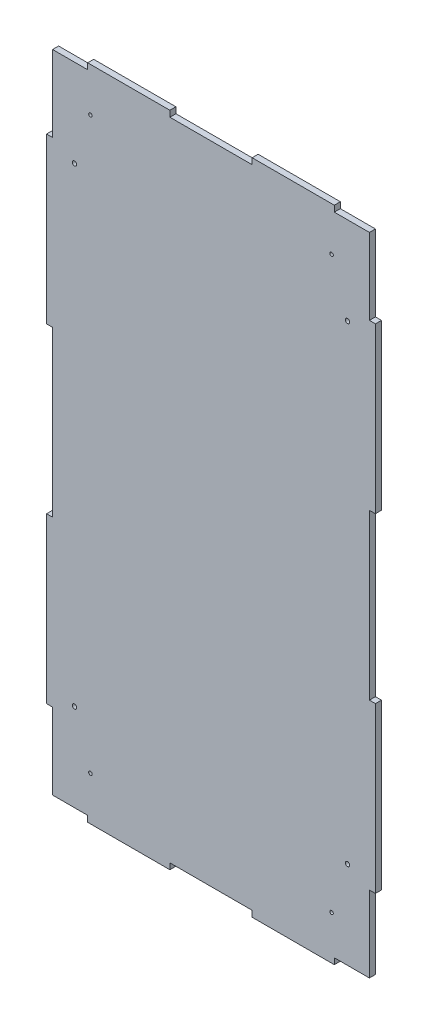
SolidWorks part; units mm, degrees
ref_plane "Front Plane" through (0, 0, 0) normal (0, 0, 1) x (1, 0, 0)
ref_plane "Top Plane" through (0, 0, 0) normal (0, 1, 0) x (1, 0, 0)
ref_plane "Right Plane" through (0, 0, 0) normal (1, 0, 0) x (0, 0, -1)
sketch "Sketch1" plane through (0, 0, 0) normal (0, 0, 1) x (1, 0, 0)
  line L0 (-0.0027, 588.9972) -> (-0.0027, 519.4972)
  line L1 (-0.0027, 519.4972) -> (-5.5027, 519.4972)
  line L2 (-5.5027, 519.4972) -> (-5.5027, 446.1222)
  line L3 (-5.5027, 446.1222) -> (-2.2527, 446.1222)
  line L4 (-2.2527, 446.1222) -> (-2.2527, 444.4972)
  line L5 (-2.2527, 444.4972) -> (-2.2527, 442.8722)
  line L6 (-2.2527, 442.8722) -> (-5.5027, 442.8722)
  line L7 (-5.5027, 442.8722) -> (-5.5027, 369.4972)
  line L8 (-5.5027, 369.4972) -> (-0.0027, 369.4972)
  line L9 (-0.0027, 369.4972) -> (-0.0027, 219.4972)
  line L10 (-0.0027, 219.4972) -> (-5.5027, 219.4972)
  line L11 (-5.5027, 219.4972) -> (-5.5027, 146.1222)
  line L12 (-5.5027, 146.1222) -> (-2.2527, 146.1222)
  line L13 (-2.2527, 146.1222) -> (-2.2527, 144.4972)
  line L14 (-2.2527, 144.4972) -> (-2.2527, 142.8722)
  line L15 (-2.2527, 142.8722) -> (-5.5027, 142.8722)
  line L16 (-5.5027, 142.8722) -> (-5.5027, 69.4972)
  line L17 (-5.5027, 69.4972) -> (-0.0027, 69.4972)
  line L18 (-0.0027, 69.4972) -> (-0.0027, -0.0028)
  line L19 (-0.0027, -0.0028) -> (31.9973, -0.0028)
  line L20 (31.9973, -0.0028) -> (31.9973, -5.5028)
  line L21 (31.9973, -5.5028) -> (67.8723, -5.5028)
  line L22 (67.8723, -5.5028) -> (67.8723, -2.2528)
  line L23 (67.8723, -2.2528) -> (69.4973, -2.2528)
  line L24 (69.4973, -2.2528) -> (71.1223, -2.2528)
  line L25 (71.1223, -2.2528) -> (71.1223, -5.5028)
  line L26 (71.1223, -5.5028) -> (106.9973, -5.5028)
  line L27 (106.9973, -5.5028) -> (106.9973, -0.0028)
  line L28 (106.9973, -0.0028) -> (181.9973, -0.0028)
  line L29 (181.9973, -0.0028) -> (181.9973, -5.5028)
  line L30 (181.9973, -5.5028) -> (217.8723, -5.5028)
  line L31 (217.8723, -5.5028) -> (217.8723, -2.2528)
  line L32 (217.8723, -2.2528) -> (219.4973, -2.2528)
  line L33 (219.4973, -2.2528) -> (221.1223, -2.2528)
  line L34 (221.1223, -2.2528) -> (221.1223, -5.5028)
  line L35 (221.1223, -5.5028) -> (256.9973, -5.5028)
  line L36 (256.9973, -5.5028) -> (256.9973, -0.0028)
  line L37 (256.9973, -0.0028) -> (288.9973, -0.0028)
  line L38 (288.9973, -0.0028) -> (288.9973, 69.4972)
  line L39 (288.9973, 69.4972) -> (294.4973, 69.4972)
  line L40 (294.4973, 69.4972) -> (294.4973, 142.8722)
  line L41 (294.4973, 142.8722) -> (291.2473, 142.8722)
  line L42 (291.2473, 142.8722) -> (291.2473, 144.4972)
  line L43 (291.2473, 144.4972) -> (291.2473, 146.1222)
  line L44 (291.2473, 146.1222) -> (294.4973, 146.1222)
  line L45 (294.4973, 146.1222) -> (294.4973, 219.4972)
  line L46 (294.4973, 219.4972) -> (288.9973, 219.4972)
  line L47 (288.9973, 219.4972) -> (288.9973, 369.4972)
  line L48 (288.9973, 369.4972) -> (294.4973, 369.4972)
  line L49 (294.4973, 369.4972) -> (294.4973, 442.8722)
  line L50 (294.4973, 442.8722) -> (291.2473, 442.8722)
  line L51 (291.2473, 442.8722) -> (291.2473, 444.4972)
  line L52 (291.2473, 444.4972) -> (291.2473, 446.1222)
  line L53 (291.2473, 446.1222) -> (294.4973, 446.1222)
  line L54 (294.4973, 446.1222) -> (294.4973, 519.4972)
  line L55 (294.4973, 519.4972) -> (288.9973, 519.4972)
  line L56 (288.9973, 519.4972) -> (288.9973, 588.9972)
  line L57 (288.9973, 588.9972) -> (256.9973, 588.9972)
  line L58 (256.9973, 588.9972) -> (256.9973, 594.4972)
  line L59 (256.9973, 594.4972) -> (221.1223, 594.4972)
  line L60 (221.1223, 594.4972) -> (221.1223, 591.2472)
  line L61 (221.1223, 591.2472) -> (219.4973, 591.2472)
  line L62 (219.4973, 591.2472) -> (217.8723, 591.2472)
  line L63 (217.8723, 591.2472) -> (217.8723, 594.4972)
  line L64 (217.8723, 594.4972) -> (181.9973, 594.4972)
  line L65 (181.9973, 594.4972) -> (181.9973, 588.9972)
  line L66 (181.9973, 588.9972) -> (106.9973, 588.9972)
  line L67 (106.9973, 588.9972) -> (106.9973, 594.4972)
  line L68 (106.9973, 594.4972) -> (71.1223, 594.4972)
  line L69 (71.1223, 594.4972) -> (71.1223, 591.2472)
  line L70 (71.1223, 591.2472) -> (69.4973, 591.2472)
  line L71 (69.4973, 591.2472) -> (67.8723, 591.2472)
  line L72 (67.8723, 591.2472) -> (67.8723, 594.4972)
  line L73 (67.8723, 594.4972) -> (31.9973, 594.4972)
  line L74 (31.9973, 594.4972) -> (31.9973, 588.9972)
  line L75 (31.9973, 588.9972) -> (-0.0027, 588.9972)
sketch "Sketch2" plane through (0, 0, 0) normal (0, 0, 1) x (1, 0, 0)
  line L0 (181.9973, 588.9972) -> (106.9973, 588.9972) construction
  line L1 (19.9973, 508.9972) -> (268.9973, 508.9972)
  line L2 (19.9973, 508.9972) -> (19.9973, 79.9972)
  line L3 (19.9973, 79.9972) -> (268.9973, 79.9972)
  line L4 (268.9973, 508.9972) -> (268.9973, 79.9972)
  line L5 (-0.0027, 588.9972) -> (-0.0027, 519.4972) construction
  line L6 (-0.0027, 369.4972) -> (-0.0027, 219.4972) construction
  circle A0 centre (19.9973, 508.9972) radius 2
  circle A1 centre (268.9973, 508.9972) radius 2
  circle A2 centre (268.9973, 79.9972) radius 2
  circle A3 centre (19.9973, 79.9972) radius 2
  point P12 (144.4973, 508.9972)
  point P13 (144.4973, 588.9972)
  point P14 (19.9973, 294.4972)
  point P17 (-0.0027, 294.4972)
  dimension "D3" = 4
  dimension "D1" = 80
  dimension "D2" = 20
extrude "Boss-Extrude1" add sketch "Sketch1" along normal blind 5.5
extrude "Cut-Extrude1" cut sketch "Sketch2" against normal through all and the other way through all contours L4 A1 L1 | L1 A1 L4 | L2 A0 L1 | L1 A0 L2 | L2 A3 L3 | L3 A3 L2 | L3 A2 L4 | L4 A2 L3 region at (19.7144, 509.2801, 0) region at (20.8461, 508.1484, 0) region at (269.2803, 509.2801, 0) region at (268.1485, 508.1484, 0) region at (20.8461, 80.846, 0) region at (19.7144, 79.7143, 0) region at (269.2803, 79.7143, 0) region at (268.1485, 80.846, 0)
sketch "Sketch3" plane through (0, 0, 5.5) normal (0, 0, 1) x (1, 0, 0)
  line L1 (34.4973, 554.4972) -> (254.4973, 554.4972)
  line L2 (34.4973, 554.4972) -> (34.4973, 34.4972)
  line L3 (34.4973, 34.4972) -> (254.4973, 34.4972)
  line L4 (254.4973, 554.4972) -> (254.4973, 34.4972)
  line L6 (-5.5027, 519.4972) -> (-5.5027, 446.1222) construction
  line L7 (294.4973, 446.1222) -> (294.4973, 519.4972) construction
  line L8 (217.8723, 594.4972) -> (181.9973, 594.4972) construction
  line L9 (181.9973, -5.5028) -> (217.8723, -5.5028) construction
  circle A0 centre (34.4973, 554.4972) radius 1.6
  circle A1 centre (254.4973, 554.4972) radius 1.6
  circle A2 centre (34.4973, 34.4972) radius 1.6
  circle A3 centre (254.4973, 34.4972) radius 1.6
  dimension "D5" = 3.2
  dimension "D1" = 40
  dimension "D2" = 40
  dimension "D3" = 40
  dimension "D4" = 40
extrude "Cut-Extrude2" cut sketch "Sketch3" against normal through all contours A0 | A1 | A2 | A3
sketch "Sketch4" plane through (0, 0, 5.5) normal (0, 0, 1) x (1, 0, 0)
  line L1 (67.8723, -5.5028) -> (71.1223, -5.5028)
  line L2 (67.8723, -5.5028) -> (67.8723, -2.2528)
  line L3 (67.8723, -2.2528) -> (71.1223, -2.2528)
  line L4 (71.1223, -5.5028) -> (71.1223, -2.2528)
  line L5 (221.1223, -2.2528) -> (217.8723, -2.2528)
  line L6 (221.1223, -2.2528) -> (221.1223, -5.5028)
  line L7 (221.1223, -5.5028) -> (217.8723, -5.5028)
  line L8 (217.8723, -2.2528) -> (217.8723, -5.5028)
  line L9 (294.4973, 146.1222) -> (291.2473, 146.1222)
  line L10 (294.4973, 146.1222) -> (294.4973, 142.8722)
  line L11 (294.4973, 142.8722) -> (291.2473, 142.8722)
  line L12 (291.2473, 146.1222) -> (291.2473, 142.8722)
  line L13 (294.4973, 446.1222) -> (291.2473, 446.1222)
  line L14 (294.4973, 446.1222) -> (294.4973, 442.8722)
  line L15 (294.4973, 442.8722) -> (291.2473, 442.8722)
  line L16 (291.2473, 446.1222) -> (291.2473, 442.8722)
  line L17 (217.8723, 591.2472) -> (221.1223, 591.2472)
  line L18 (217.8723, 591.2472) -> (217.8723, 594.4972)
  line L19 (217.8723, 594.4972) -> (221.1223, 594.4972)
  line L20 (221.1223, 591.2472) -> (221.1223, 594.4972)
  line L21 (71.1223, 594.4972) -> (67.8723, 594.4972)
  line L22 (71.1223, 594.4972) -> (71.1223, 591.2472)
  line L23 (71.1223, 591.2472) -> (67.8723, 591.2472)
  line L24 (67.8723, 594.4972) -> (67.8723, 591.2472)
  line L25 (-2.2527, 446.1222) -> (-5.5027, 446.1222)
  line L26 (-2.2527, 446.1222) -> (-2.2527, 442.8722)
  line L27 (-2.2527, 442.8722) -> (-5.5027, 442.8722)
  line L28 (-5.5027, 446.1222) -> (-5.5027, 442.8722)
  line L29 (-2.2527, 146.1222) -> (-5.5027, 146.1222)
  line L30 (-2.2527, 146.1222) -> (-2.2527, 142.8722)
  line L31 (-2.2527, 142.8722) -> (-5.5027, 142.8722)
  line L32 (-5.5027, 146.1222) -> (-5.5027, 142.8722)
extrude "Boss-Extrude2" add sketch "Sketch4" against normal up to surface (5.5 mm away) up to face at (256.0973, 554.4972, 0)
